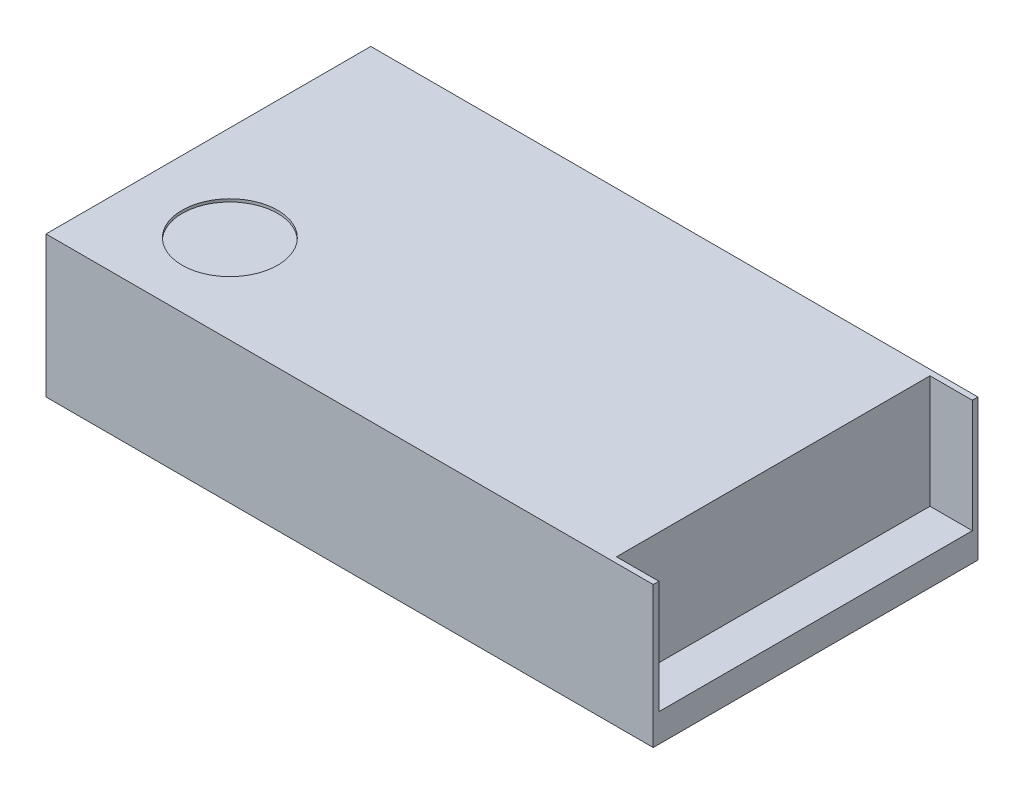
SolidWorks part; units mm, degrees
ref_plane "Front Plane" through (0, 0, 0) normal (0, 0, 1) x (1, 0, 0)
ref_plane "Top Plane" through (0, 0, 0) normal (0, 1, 0) x (1, 0, 0)
ref_plane "Right Plane" through (0, 0, 0) normal (1, 0, 0) x (0, 0, -1)
sketch "Sketch1" plane through (0, 0, 0) normal (0, 1, 0) x (1, 0, 0)
  line L1 (-107.5, -57.5) -> (107.5, -57.5)
  line L2 (-107.5, -57.5) -> (-107.5, 57.5)
  line L3 (-107.5, 57.5) -> (107.5, 57.5)
  line L4 (107.5, -57.5) -> (107.5, 57.5)
  line L5 (-107.5, -57.5) -> (107.5, 57.5) construction
  line L6 (-107.5, 57.5) -> (107.5, -57.5) construction
  point P0 (0, 0)
  dimension "D1" = 215
  dimension "D2" = 115
extrude "Boss-Extrude1" add sketch "Sketch1" along normal blind 50
sketch "Sketch2" plane through (0, 50, 0) normal (0, 1, 0) x (1, 0, 0)
  circle A0 centre (-73.7948, -26.1004) radius 16.8996
extrude "Cut-Extrude1" cut sketch "Sketch2" against normal blind 1
sketch "Sketch4" plane through (0, 50, 0) normal (0, 1, 0) x (1, 0, 0)
  line L0 (107.5, -57.5) -> (107.5, 57.5) construction
  line L1 (107.5, 55.5) -> (92.5, 55.5)
  line L2 (107.5, 55.5) -> (107.5, -55.5)
  line L3 (107.5, -55.5) -> (92.5, -55.5)
  line L4 (92.5, 55.5) -> (92.5, -55.5)
  line L5 (107.5, 57.5) -> (-107.5, 57.5) construction
  line L6 (-107.5, -57.5) -> (107.5, -57.5) construction
  point P6 (107.5, -40.732)
  dimension "D1" = 2
  dimension "D2" = 2
  dimension "D3" = 15
extrude "Cut-Extrude2" cut sketch "Sketch4" against normal blind 40
equation "\"D2@Sketch4\"=\"D1@Sketch4\""
